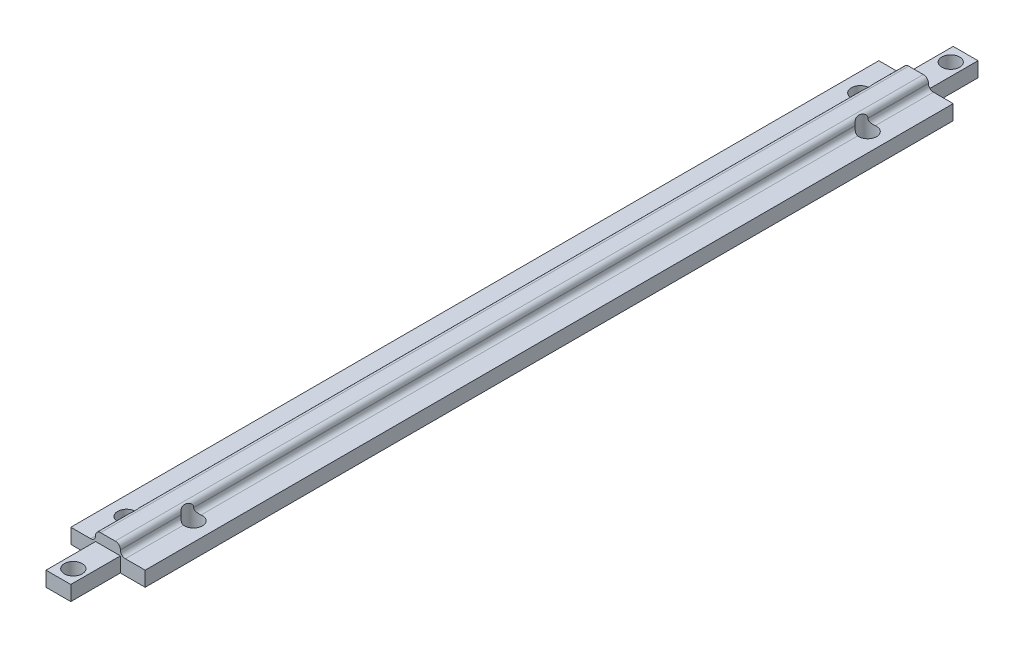
SolidWorks part; units mm, degrees
ref_plane "Front Plane" through (0, 0, 0) normal (0, 0, 1) x (1, 0, 0)
ref_plane "Top Plane" through (0, 0, 0) normal (0, 1, 0) x (1, 0, 0)
ref_plane "Right Plane" through (0, 0, 0) normal (1, 0, 0) x (0, 0, -1)
sketch "Sketch1" plane through (0, 0, 0) normal (0, 1, 0) x (1, 0, 0)
  line L1 (-2.5, -81.5) -> (2.5, -81.5)
  line L2 (-2.5, -81.5) -> (-2.5, 81.5)
  line L3 (-2.5, 81.5) -> (2.5, 81.5)
  line L4 (2.5, -81.5) -> (2.5, 81.5)
  line L5 (-2.5, -81.5) -> (2.5, 81.5) construction
  line L6 (-2.5, 81.5) -> (2.5, -81.5) construction
  point P0 (0, 0)
  dimension "D1" = 5
  dimension "D2" = 163
extrude "Boss-Extrude1" add sketch "Sketch1" along normal blind 3
ref_plane "Plane3" through (0, 0, 0) normal (0, 0, 1) x (1, 0, 0)
sketch "Sketch3" plane through (0, 0, 0) normal (0, 0, 1) x (1, 0, 0)
  line L0 (-2.5, 3) -> (-2.5, 5.103)
  line L1 (-2.5, 5.103) -> (2.5, 5.103) construction
  line L2 (2.5, 5.103) -> (2.5, 3)
  line L3 (0, 5.103) -> (0, 64.05) construction
  line L4 (-2.5, 0) -> (2.5, 0)
  line L5 (2.5, 0) -> (2.5, 3)
  line L6 (2.5, 3) -> (-2.5, 3)
  line L7 (-2.5, 3) -> (-2.5, 0)
  line L8 (-2.5, 0) -> (2.5, 0)
  line L9 (2.5, 0) -> (2.5, 3)
  line L11 (-2.5, 3) -> (-2.5, 0)
  arc A0 (-2.5, 5.103) -> (2.5, 5.103) centre (0, 64.05) ccw
  dimension "D1" = 0
extrude "Boss-Extrude2" add sketch "Sketch3" along normal up to surface (81.5 mm away) up to face at (0, 1.5, 81.5)
sketch "Sketch7" plane through (0, 0, 0) normal (0, 0, -1) x (-1, 0, 0)
  line L3 (-2.5, 5.103) -> (-2.5, 3)
  line L4 (-2.5, 3) -> (2.5, 3)
  line L5 (2.5, 3) -> (2.5, 5.103)
  line L6 (-2.5, 5.103) -> (-2.5, 3)
  line L7 (-2.5, 3) -> (2.5, 3)
  line L8 (2.5, 3) -> (2.5, 5.103)
  arc A1 (-2.5, 5.103) -> (2.5, 5.103) centre (0, 64.05) ccw
  arc A2 (-2.5, 5.103) -> (2.5, 5.103) centre (0, 64.05) ccw
  dimension "D1" = 0
extrude "Boss-Extrude3" add sketch "Sketch7" along normal up to surface (81.5 mm away) up to face at (0, 1.5, -81.5)
sketch "Sketch8" plane through (0, 0, 0) normal (0, -1, 0) x (1, 0, 0)
  line L0 (2.5, 81.5) -> (2.5, -81.5) construction
  line L1 (-2.5, 81.5) -> (2.5, 81.5)
  line L2 (-2.5, 81.5) -> (-2.5, 91.5)
  line L3 (-2.5, 91.5) -> (2.5, 91.5)
  line L4 (2.5, 81.5) -> (2.5, 91.5)
  line L5 (0, 0) -> (17.0745, 0) construction
  line L6 (-2.5, -91.5) -> (2.5, -91.5)
  line L7 (2.5, -81.5) -> (2.5, -91.5)
  line L8 (-2.5, -81.5) -> (2.5, -81.5)
  line L9 (-2.5, -81.5) -> (-2.5, -91.5)
  dimension "D1" = 10
extrude "Boss-Extrude4" add sketch "Sketch8" against normal blind 3
sketch "Sketch6" plane through (0, 3, 0) normal (0, 1, 0) x (1, 0, 0)
  line L0 (0, -91.5) -> (0, -88.5) construction
  line L2 (0, 0) -> (12.4428, 0) construction
  line L3 (-5.6053, 0) -> (5.6053, 0) construction
  line L4 (2.5, -91.5) -> (-2.5, -91.5) construction
  circle A0 centre (0, -88.5) radius 1.8
  circle A1 centre (0, 88.5) radius 1.8
  dimension "D1" = 3.6
  dimension "D2" = 3
extrude "Cut-Extrude1" cut sketch "Sketch6" against normal through all
sketch "Sketch9" plane through (0, 0, 0) normal (0, -1, 0) x (1, 0, 0)
  line L0 (2.5, -81.5) -> (-2.5, -81.5) construction
  line L1 (-2.5, 81.5) -> (2.5, 81.5) construction
  line L2 (2.5, -81.5) -> (-2.5, -81.5) construction
  line L3 (-2.5, 81.5) -> (2.5, 81.5) construction
  line L4 (-2.5, -91.5) -> (-2.5, 91.5) construction
  line L5 (-7.5, -81.5) -> (7.5, -81.5)
  line L6 (-7.5, -81.5) -> (-7.5, 81.5)
  line L7 (-7.5, 81.5) -> (7.5, 81.5)
  line L8 (7.5, -81.5) -> (7.5, 81.5)
  line L9 (-2.5, -91.5) -> (-2.5, 91.5) construction
  point P8 (0, -81.5)
  point P9 (0, -81.5)
  point P10 (0, 81.5)
  point P11 (0, 81.5)
  dimension "D1" = 5
extrude "Boss-Extrude5" add sketch "Sketch9" against normal up to surface (3 mm away) up to face at (0, 3, 90.3)
fillet "Fillet1" radius 1 4 edges at (-2.5, 5.103, 0) (2.5, 5.103, 0) (2.5, 3, 0) (-2.5, 3, 0)
sketch "Sketch10" plane through (0, 3, 0) normal (0, 1, 0) x (1, 0, 0)
  line L0 (0, -81.5) -> (0, -74) construction
  line L1 (-1.475, -81.5) -> (1.475, -81.5) construction
  line L2 (0, -74) -> (-3.75, -74) construction
  line L3 (-3.75, -74) -> (-7.5, -74) construction
  line L4 (-7.5, -81.5) -> (-7.5, 81.5) construction
  line L5 (0, -74) -> (0, -68) construction
  line L6 (0, -68) -> (3.75, -68) construction
  line L7 (3.75, -68) -> (7.5, -68) construction
  line L8 (7.5, 81.5) -> (7.5, -81.5) construction
  line L9 (-3.5, -81.5) -> (-7.5, -81.5) construction
  line L10 (-7.5, 0) -> (7.5, 0) construction
  circle A0 centre (-3.75, -74) radius 1.8
  circle A1 centre (3.75, -68) radius 1.8
  circle A2 centre (3.75, 68) radius 1.8
  circle A3 centre (-3.75, 74) radius 1.8
  dimension "D1" = 3.6
  dimension "D2" = 6
  dimension "D3" = 7.5
extrude "Cut-Extrude2" cut sketch "Sketch10" against normal through all both and the other way through all
